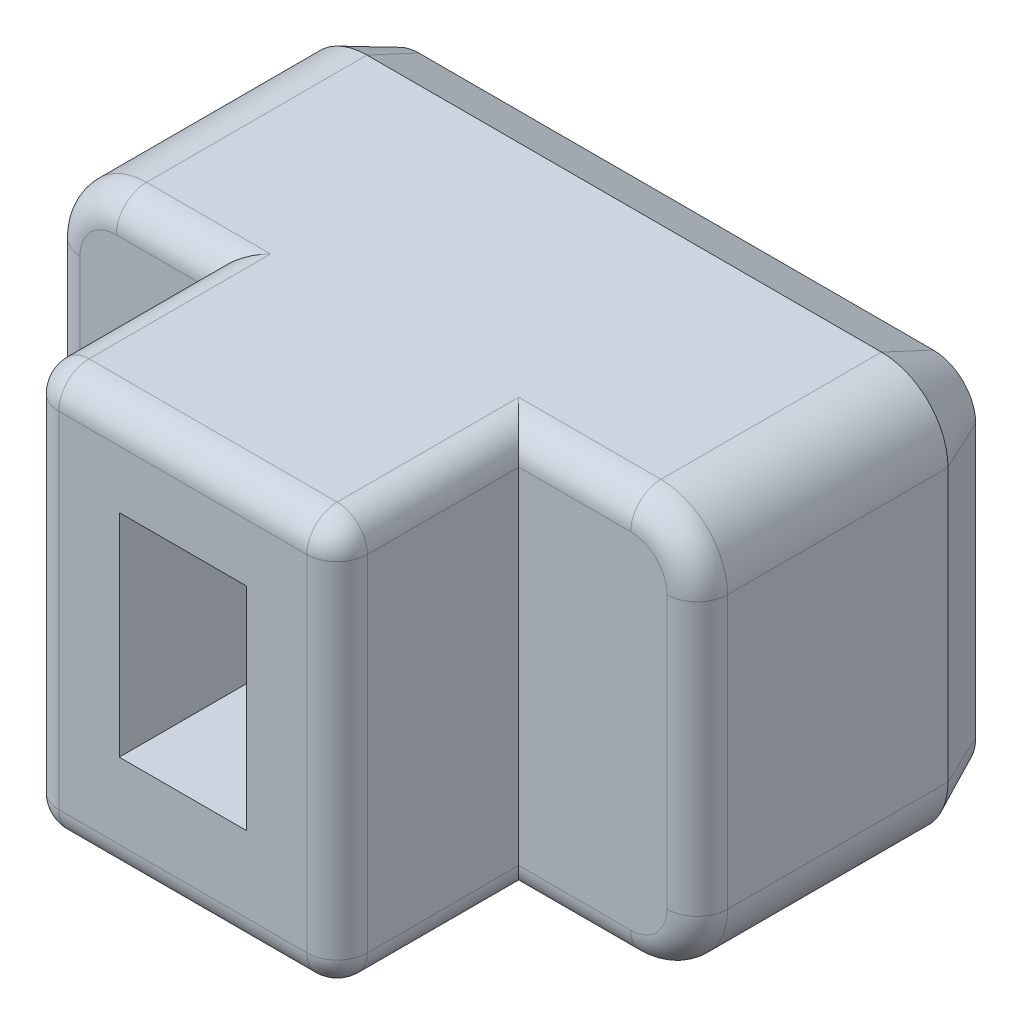
SolidWorks part; units mm, degrees
ref_plane "Plan de face" through (0, 0, 0) normal (0, 0, 1) x (1, 0, 0)
ref_plane "Plan de dessus" through (0, 0, 0) normal (0, 1, 0) x (1, 0, 0)
ref_plane "Plan de droite" through (0, 0, 0) normal (1, 0, 0) x (0, 0, -1)
sketch "Esquisse2" plane through (0, 0, 0) normal (0, 0, 1) x (1, 0, 0)
  line L1 (1.1, 0) -> (9.6, 0)
  line L2 (0, 1.1) -> (0, 5.6)
  line L3 (1.1, 6.7) -> (9.6, 6.7)
  line L4 (10.7, 1.1) -> (10.7, 5.6)
  arc A0 (9.6, 6.7) -> (10.7, 5.6) centre (9.6, 5.6) cw
  arc A1 (9.6, 0) -> (10.7, 1.1) centre (9.6, 1.1) ccw
  arc A2 (1.1, 0) -> (0, 1.1) centre (1.1, 1.1) cw
  arc A3 (0, 5.6) -> (1.1, 6.7) centre (1.1, 5.6) cw
  point P7 (10.7, 6.7)
  point P12 (0, 0)
  point P15 (0, 6.7)
  dimension "D3" = 1.1
  dimension "D1" = 10.7
  dimension "D2" = 6.7
extrude "Boss.-Extru.1" add sketch "Esquisse2" along normal blind 8
sketch "Esquisse3" plane through (0, 0, 8) normal (0, 0, 1) x (1, 0, 0)
  line L0 (0, 5.6) -> (0, 1.1) construction
  line L1 (4.15, 5.25) -> (6.25, 5.25)
  line L2 (4.15, 5.25) -> (4.15, 1.75)
  line L3 (4.15, 1.75) -> (6.25, 1.75)
  line L4 (6.25, 5.25) -> (6.25, 1.75)
  line L5 (10.7, 1.1) -> (10.7, 5.6) construction
  line L6 (9.6, 6.7) -> (1.1, 6.7) construction
  line L7 (1.1, 0) -> (9.6, 0) construction
  dimension "D1" = 2.1
  dimension "D2" = 3.5
  dimension "D3" = 4.15
  dimension "D4" = 4.45
  dimension "D5" = 1.45
  dimension "D6" = 1.75
extrude "Enlèv. mat.-Extru.1" cut sketch "Esquisse3" against normal blind 3
sketch "Esquisse4" plane through (0, 0, 8) normal (0, 0, 1) x (1, 0, 0)
  line L0 (2.65, 6.7) -> (2.65, 0)
  line L1 (9.6, 6.7) -> (1.1, 6.7) construction
  line L2 (1.1, 0) -> (9.6, 0) construction
  line L3 (2.65, 0) -> (7.75, 0)
  line L4 (7.75, 0) -> (7.75, 6.7)
  line L5 (7.75, 6.7) -> (2.65, 6.7)
  line L6 (4.15, 5.25) -> (4.15, 1.75) construction
  line L7 (6.25, 1.75) -> (6.25, 5.25) construction
  dimension "D1" = 1.5
  dimension "D2" = 1.5
extrude "Enlèv. mat.-Extru.2" cut sketch "Esquisse4" against normal blind 3 flip side to cut
fillet "Congé1" radius 0.5 18 edges at (8.675, 0, 5) (10.3778, 0.3222, 5) (10.7, 3.35, 5) (10.3778, 6.3778, 5) (1.875, 6.7, 5) (0.3222, 6.3778, 5) (1.875, 0, 5) (0.3222, 0.3222, 5) (7.75, 6.7, 6.5) (2.65, 6.7, 6.5) (7.75, 0, 6.5) (2.65, 0, 6.5) (2.65, 3.35, 8) (5.2, 6.7, 8) (7.75, 3.35, 8) (5.2, 0, 8) (8.675, 6.7, 5) (0, 3.35, 5)
chamfer "Chanfrein1" distance 0.4 angle 65 8 edges at (5.35, 0, 0) (10.3778, 0.3222, 0) (0.3222, 0.3222, 0) (10.7, 3.35, 0) (0, 3.35, 0) (10.3778, 6.3778, 0) (0.3222, 6.3778, 0) (5.35, 6.7, 0) first distance on face at (5.35, 3.35, 0)
ref_plane "Plan1" through (0, 0, 0.2) normal (0, 0, 1) x (1, 0, 0)
sketch "Esquisse5" plane through (0, 0, 0.2) normal (0, 0, 1) x (1, 0, 0)
  line L0 (-0.9378, 5.3566) -> (11.6517, 5.3566) construction
  text T0 "VS+" font "Century Gothic" height 4
extrude "Enlèv. mat.-Extru.3" cut sketch "Esquisse5" against normal blind 0.3
extrude "Boss.-Extru.2" add sketch "Esquisse5<3>" against normal blind 0.2 from offset 0.2 offset against normal yes
sketch "Esquisse5<3>" plane through (0, 0, 0.2) normal (0, 0, 1) x (1, 0, 0) same geometry as "Esquisse5"
